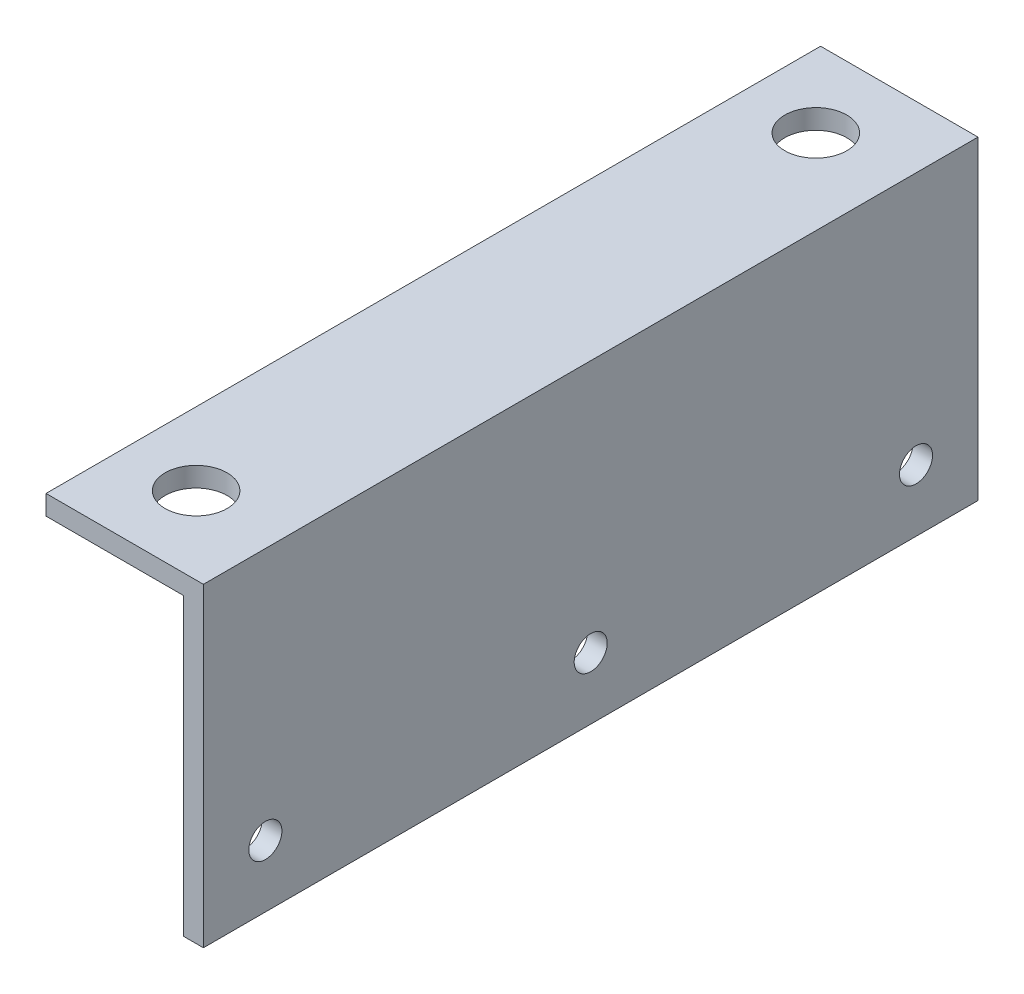
SolidWorks part; units mm, degrees
ref_plane "Front Plane" through (0, 0, 0) normal (0, 0, 1) x (1, 0, 0)
ref_plane "Top Plane" through (0, 0, 0) normal (0, 1, 0) x (1, 0, 0)
ref_plane "Right Plane" through (0, 0, 0) normal (1, 0, 0) x (0, 0, -1)
sketch "Sketch1" plane through (0, 0, 0) normal (0, 0, 1) x (1, 0, 0)
  line L0 (0, 0) -> (0, 50.8)
  line L1 (0, 50.8) -> (-25.4, 50.8)
  line L2 (-3.175, 0) -> (-3.175, 47.625)
  line L3 (-3.175, 47.625) -> (-25.4, 47.625)
  line L4 (-25.4, 50.8) -> (-25.4, 47.625)
  line L5 (-3.175, 0) -> (0, 0)
  dimension "D1" = 25.4
  dimension "D2" = 50.8
  dimension "D3" = 3.175
extrude "Boss-Extrude1" add sketch "Sketch1" along normal blind 125
sketch "Sketch2" plane through (0, 0, 0) normal (1, 0, 0) x (0, 0, -1)
  line L0 (-125, 10) -> (0, 10) construction
  line L1 (-125, 0) -> (-125, 50.8) construction
  line L2 (0, 0) -> (0, 50.8) construction
  line L3 (-125, 0) -> (0, 0) construction
  circle A0 centre (-115, 10) radius 2.665
  circle A1 centre (-10, 10) radius 2.665
  circle A2 centre (-62.5, 10) radius 2.665
  dimension "D2" = 5.33
  dimension "D3" = 10
  dimension "D4" = 10
  dimension "D1" = 10
extrude "Cut-Extrude1" cut sketch "Sketch2" against normal up to next
sketch "Sketch3" plane through (0, 50.8, 0) normal (0, 1, 0) x (1, 0, 0)
  line L0 (0, -62.5) -> (-25.4, -62.5) construction
  line L1 (0, -125) -> (0, 0) construction
  line L2 (-25.4, -125) -> (-25.4, 0) construction
  arc A0 (-13.675, -7.5) -> (-13.675, -17.5) centre (-13.675, -12.5) ccw construction
  arc A1 (-13.675, -7.5) -> (-13.675, -17.5) centre (-13.675, -12.5) ccw
  circle A2 centre (-13.675, -12.5) radius 5
  circle A3 centre (-13.675, -112.5) radius 5
extrude "Cut-Extrude2" cut sketch "Sketch3" against normal up to next contours A3 | A1 A2 region at (-13.675, 50.8, 12.5) region at (-13.675, 50.8, 112.5)
